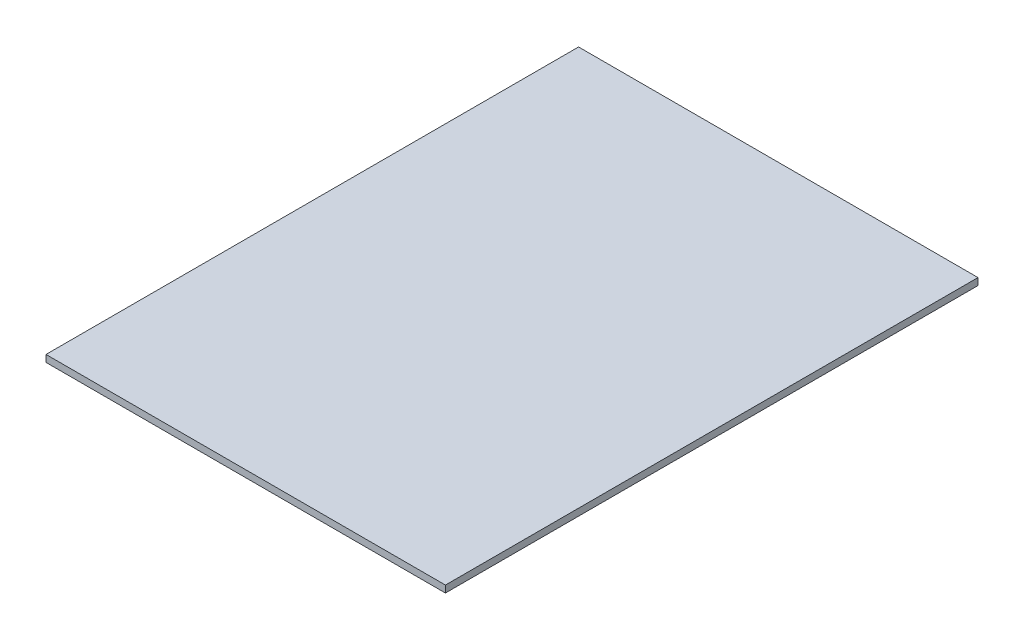
SolidWorks part; units mm, degrees
material "Pine"
ref_plane "Front Plane" through (0, 0, 0) normal (0, 0, 1) x (1, 0, 0)
ref_plane "Top Plane" through (0, 0, 0) normal (0, 1, 0) x (1, 0, 0)
ref_plane "Right Plane" through (0, 0, 0) normal (1, 0, 0) x (0, 0, -1)
sketch "Sketch1" plane through (0, 0, 0) normal (0, 1, 0) x (1, 0, 0)
  line L1 (-342.9, -457.2) -> (342.9, -457.2)
  line L2 (-342.9, -457.2) -> (-342.9, 457.2)
  line L3 (-342.9, 457.2) -> (342.9, 457.2)
  line L4 (342.9, -457.2) -> (342.9, 457.2)
  line L5 (-342.9, -457.2) -> (342.9, 457.2) construction
  line L6 (-342.9, 457.2) -> (342.9, -457.2) construction
  point P0 (0, 0)
  dimension "D1" = 685.8
  dimension "D2" = 914.4
extrude "Boss-Extrude1" add sketch "Sketch1" along normal blind 11.9062
